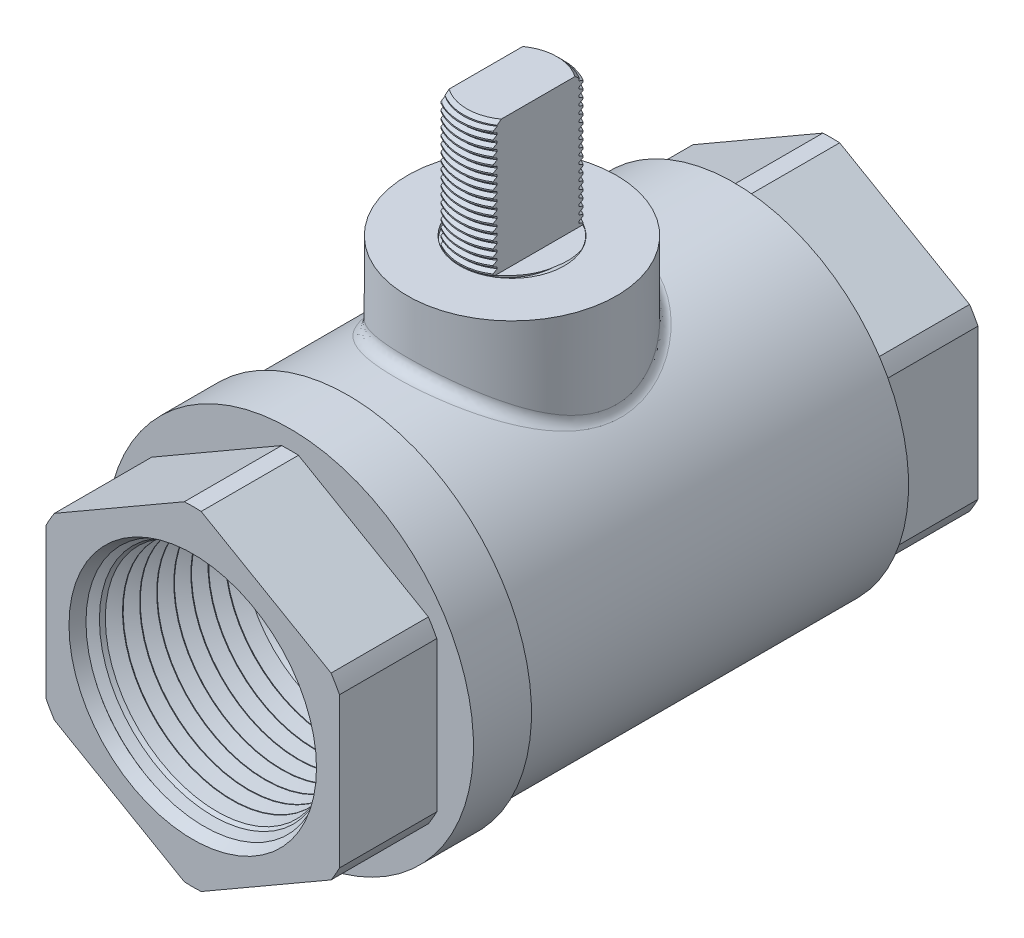
SolidWorks part; units mm, degrees
material "AISI 316 Stainless Steel Sheet (SS)"
ref_plane "Front" through (0, 0, 0) normal (0, 0, 1) x (1, 0, 0)
ref_plane "Top" through (0, 0, 0) normal (0, 1, 0) x (1, 0, 0)
ref_plane "Right" through (0, 0, 0) normal (1, 0, 0) x (0, 0, -1)
sketch "Sketch1" plane through (0, -2.9295, 125.5668) normal (1, 0, 0) x (0, 0, -1)
  line L0 (143.4992, 2.9295) -> (143.4992, 14.4244)
  line L1 (143.4992, 14.4244) -> (144.3569, 16.0232) construction
  line L2 (144.3569, 16.0232) -> (145.3126, 14.4811) construction
  line L3 (145.3126, 14.4811) -> (146.1703, 16.0799) construction
  line L4 (146.1703, 16.0799) -> (147.126, 14.5378) construction
  line L5 (145.3453, 14.542) -> (146.1376, 16.0189)
  line L6 (146.1376, 16.0189) -> (146.2067, 16.0211)
  line L7 (146.2067, 16.0211) -> (147.0896, 14.5965)
  line L8 (147.0896, 14.5965) -> (147.1587, 14.5987)
  line L9 (143.4992, 14.4244) -> (147.126, 14.5378) construction
  line L10 (144.3569, 16.0232) -> (146.1703, 16.0799) construction
  line L11 (143.9281, 15.2238) -> (146.6482, 15.3088) construction
  line L12 (143.4992, 2.9295) -> (125.5668, 2.9295) construction
  line L13 (147.1587, 14.5987) -> (147.951, 16.0756)
  line L14 (143.5319, 14.4854) -> (144.3242, 15.9622)
  line L15 (144.3242, 15.9622) -> (144.3933, 15.9644)
  line L16 (144.3933, 15.9644) -> (145.2762, 14.5399)
  line L17 (145.2762, 14.5399) -> (145.3453, 14.542)
  line L18 (143.9281, 15.2238) -> (143.4992, 15.2104) construction
  line L19 (143.4992, 15.2104) -> (143.4992, 14.4244) construction
  line L20 (143.9281, -9.3648) -> (143.4992, -9.3514) construction
  line L21 (143.5319, 14.4854) -> (143.4992, 14.4244)
  line L22 (147.951, 16.0756) -> (148.0201, 16.0777)
  line L23 (148.0201, 16.0777) -> (148.903, 14.6532)
  line L24 (148.903, 14.6532) -> (148.9721, 14.6554)
  line L25 (148.9721, 14.6554) -> (149.7644, 16.1323)
  line L26 (149.7644, 16.1323) -> (149.8335, 16.1344)
  line L27 (149.8335, 16.1344) -> (150.7164, 14.7099)
  line L28 (150.7164, 14.7099) -> (150.7855, 14.712)
  line L29 (150.7855, 14.712) -> (151.5778, 16.1889)
  line L30 (151.5778, 16.1889) -> (151.6469, 16.1911)
  line L31 (151.6469, 16.1911) -> (152.5298, 14.7666)
  line L32 (152.5298, 14.7666) -> (152.5989, 14.7687)
  line L33 (152.5989, 14.7687) -> (153.3912, 16.2456)
  line L34 (153.3912, 16.2456) -> (153.4603, 16.2478)
  line L35 (153.4603, 16.2478) -> (154.3432, 14.8232)
  line L36 (154.3432, 14.8232) -> (154.4123, 14.8254)
  line L37 (154.4123, 14.8254) -> (155.2046, 16.3023)
  line L38 (155.2046, 16.3023) -> (155.2737, 16.3044)
  line L39 (155.2737, 16.3044) -> (156.1566, 14.8799)
  line L40 (156.1566, 14.8799) -> (156.2257, 14.8821)
  line L41 (156.2257, 14.8821) -> (157.018, 16.3589)
  line L42 (157.018, 16.3589) -> (157.0871, 16.3611)
  line L43 (157.0871, 16.3611) -> (157.97, 14.9366)
  line L44 (157.97, 14.9366) -> (158.0391, 14.9387)
  line L45 (158.0391, 14.9387) -> (158.8314, 16.4156)
  line L46 (158.8314, 16.4156) -> (158.9005, 16.4178)
  line L47 (158.9005, 16.4178) -> (159.7834, 14.9932)
  line L48 (159.7834, 14.9932) -> (159.8525, 14.9954)
  line L49 (159.8525, 14.9954) -> (160.6448, 16.4723)
  line L50 (160.6448, 16.4723) -> (160.7139, 16.4744)
  line L51 (160.7139, 16.4744) -> (161.5968, 15.0499)
  line L52 (161.5968, 15.0499) -> (161.6659, 15.0521)
  line L53 (161.6659, 15.0521) -> (162.4582, 16.529)
  line L54 (162.4582, 16.529) -> (162.5273, 16.5311)
  line L55 (162.5273, 16.5311) -> (163.4102, 15.1066)
  line L56 (163.4102, 15.1066) -> (163.4793, 15.1087)
  line L57 (163.4793, 15.1087) -> (164.2716, 16.5856)
  line L58 (164.2716, 16.5856) -> (164.3407, 16.5878)
  line L59 (164.3407, 16.5878) -> (165.2236, 15.1633)
  line L60 (165.2236, 15.1633) -> (165.2927, 15.1654)
  line L61 (165.2927, 15.1654) -> (166.085, 16.6423)
  line L62 (166.085, 16.6423) -> (166.1541, 16.6445)
  line L63 (166.1541, 16.6445) -> (167.037, 15.2199)
  line L64 (167.037, 15.2199) -> (167.1061, 15.2221)
  line L65 (167.1061, 15.2221) -> (167.8984, 16.699)
  line L66 (167.8984, 16.699) -> (167.9675, 16.7011)
  line L67 (167.9675, 16.7011) -> (168.8504, 15.2766)
  line L68 (168.8504, 15.2766) -> (168.9195, 15.2788)
  line L69 (168.9195, 15.2788) -> (169.7118, 16.7556)
  line L70 (169.7118, 16.7556) -> (169.7809, 16.7578)
  line L71 (169.7809, 16.7578) -> (170.6638, 15.3333)
  line L72 (170.6638, 15.3333) -> (170.7329, 15.3354)
  line L73 (143.4992, 2.9295) -> (170.7329, 2.9295)
  line L74 (170.7329, 2.9295) -> (170.7329, 15.3354)
  line L75 (144.3587, 15.9633) -> (144.3569, 16.0232) construction
  line L76 (146.6482, 15.3088) -> (157.3676, 15.6438) construction
  line L77 (157.3676, 15.6438) -> (157.3676, 2.9295) construction
  line L78 (157.3676, 15.6438) -> (160.4918, 15.7414) construction
  line L79 (160.4918, 15.7414) -> (160.4918, 2.9295) construction
  line L84 (157.3676, 14.9177) -> (160.4918, 15.0154) construction
  line L85 (143.4992, 8.677) -> (125.5668, 8.677) construction
  line L86 (125.5668, 8.677) -> (125.5668, 2.9295) construction
  dimension "D1" = 60
  dimension "E0" = 24.5618
  dimension "Thread Pitch" = 1.8143
  dimension "D4" = 3.58
  dimension "L2 Thread Engagement" = 13.8684
  dimension "l Thread Length" = 16.9926
  dimension "Body Length" = 69.85
revolve "Revolve1" add sketch "Sketch1" angle 360 about L12
sketch "Sketch6" plane through (0, 0, 0) normal (1, 0, 0) x (0, 0, -1)
  line L0 (34.925, 0) -> (34.925, 13.538)
  line L1 (34.925, 13.538) -> (45.1661, 13.8581)
  line L2 (45.1661, 13.8581) -> (45.1661, 0)
  line L3 (45.1661, 0) -> (34.925, 0)
  line L4 (34.925, 12.8119) -> (34.925, 0) construction
  line L5 (17.9324, 0) -> (45.1661, 0) construction
  line L6 (45.1661, 0) -> (45.1661, 12.4059) construction
  line L7 (35.0779, 13.5428) -> (35.1471, 13.5449) construction
revolve "Cut-Revolve3" cut sketch "Sketch6" angle 360 about L3
sketch "Sketch7" plane through (0, 0, 0) normal (1, 0, 0) x (0, 0, -1)
  line L0 (31.8008, 11.9882) -> (34.925, 13.538)
  line L1 (34.925, 13.538) -> (34.925, 12.0859)
  line L2 (34.925, 12.0859) -> (31.8008, 11.9882)
  line L3 (34.925, 12.8119) -> (34.925, 0) construction
  line L4 (18.7573, 13.0327) -> (18.8265, 13.0349) construction
  line L5 (31.8008, 11.9882) -> (34.925, 12.0859) construction
  line L6 (17.9324, 0) -> (31.8008, 0) construction
  line L7 (31.8008, 0) -> (31.8008, 11.9882) construction
  line L8 (17.9324, 0) -> (17.9324, 11.4949) construction
  line L9 (0, 0) -> (17.9324, 0)
  line L10 (0, 0) -> (0, 10.16)
  line L11 (0, 10.16) -> (16.5975, 10.16)
  line L12 (17.9324, 0) -> (17.9324, 11.4949)
  line L13 (17.9324, 11.4949) -> (16.5975, 10.16)
  dimension "D1" = 45
  dimension "Min ID" = 20.32
revolve "Revolve3" add sketch "Sketch7" angle 360 about L6
mirror "Mirror2" about plane through (0, 0, 0) normal (0, 0, 1) of bodies 114
sketch "Sketch8" plane through (0, 0, 34.925) normal (0, 0, 1) x (1, 0, 0)
  line L1 (0, 18.5362) -> (-16.0528, 9.2681)
  line L2 (-16.0528, 9.2681) -> (-16.0528, -9.2681)
  line L3 (-16.0528, -9.2681) -> (0, -18.5362)
  line L4 (0, -18.5362) -> (16.0528, -9.2681)
  line L5 (16.0528, -9.2681) -> (16.0528, 9.2681)
  line L6 (16.0528, 9.2681) -> (0, 18.5362)
  circle A0 centre (0, 0) radius 16.0528 construction
  dimension "Body Hex" = 32.1056
extrude "Extrude1" add sketch "Sketch8" against normal up to surface (69.85 mm away) separate body
sketch "Sketch9" plane through (0, 0, 0) normal (1, 0, 0) x (0, 0, -1)
  line L0 (-24.2824, 9.2681) -> (-24.2824, 20.066)
  line L1 (-24.2824, 20.066) -> (-17.9324, 20.066)
  line L2 (-17.9324, 20.066) -> (-17.9324, 19.5009)
  line L3 (-17.9324, 19.5009) -> (-17.5328, 19.1013)
  line L4 (-17.5328, 19.1013) -> (24.2824, 19.1013)
  line L5 (24.2824, 19.1013) -> (24.2824, 9.2681)
  line L6 (24.2824, 9.2681) -> (-24.2824, 9.2681)
  line L7 (34.925, 9.2681) -> (-34.925, 9.2681) construction
  line L8 (0, 0) -> (0, 9.2681) construction
  line L9 (17.9324, 0) -> (17.9324, 11.4949) construction
  line L10 (0, 0) -> (-24.2824, 0) construction
  line L11 (-24.2824, 0) -> (-24.2824, 9.2681) construction
  line L12 (-17.5328, 19.1013) -> (-17.5328, 18.5362) construction
  line L13 (34.925, 18.5362) -> (-34.925, 18.5362) construction
  line L14 (34.925, 12.8119) -> (34.925, 19.1013) construction
  line L15 (34.925, 19.1013) -> (24.2824, 19.1013) construction
  dimension "D1" = 6.35
  dimension "D2" = 40.132
  dimension "D3" = 135
  dimension "D4" = 6.35
revolve "Revolve4" add sketch "Sketch9" angle 360 about L10
sketch "Sketch10" plane through (0, 0, 0) normal (1, 0, 0) x (0, 0, -1)
  line L0 (0, 1.27) -> (0, 25.4259)
  line L1 (5.7023, 26.2133) -> (5.7277, 26.2133) construction
  line L2 (11.43, 26.2133) -> (11.43, 1.27)
  line L3 (11.43, 1.27) -> (0, 1.27)
  line L4 (0, 0) -> (0, 1.27) construction
  line L5 (-12.7, 21.3873) -> (-12.7, 26.4673) construction
  line L6 (-12.7, 26.4673) -> (12.7, 26.4673) construction
  line L7 (12.7, 26.4673) -> (55.4625, 46.4078) construction
  line L8 (-12.7, 21.3873) -> (-15.875, 21.3873) construction
  line L9 (-15.875, 21.3873) -> (-15.875, 29.6423) construction
  line L10 (-15.875, 29.6423) -> (11.9961, 29.6423) construction
  line L11 (11.9961, 29.6423) -> (55.4625, 49.911) construction
  line L12 (55.4625, 49.911) -> (55.4625, 46.4078) construction
  line L13 (24.2824, 19.1013) -> (-17.5328, 19.1013) construction
  line L14 (55.4625, 51.816) -> (55.4625, 44.5028) construction
  line L15 (55.4625, 44.5028) -> (127, 44.5028) construction
  line L16 (127, 44.5028) -> (127, 51.816) construction
  line L17 (127, 51.816) -> (55.4625, 51.816) construction
  line L18 (-1.9394, 29.6423) -> (-1.9394, 26.4673) construction
  line L19 (33.7293, 39.7766) -> (35.0711, 36.8991) construction
  line L20 (-11.43, 26.2133) -> (-11.43, 1.27) construction
  line L22 (55.4625, 44.5028) -> (55.4625, 10.1859) construction
  line L23 (24.2824, 19.1013) -> (-17.5328, 19.1013) construction
  line L26 (5.7023, 26.2133) -> (5.7023, 40.6913)
  line L27 (5.7023, 40.6913) -> (0, 40.6913)
  line L28 (5.7023, 26.2133) -> (5.7023, 25.4513)
  line L29 (5.7023, 25.4513) -> (0, 25.4513)
  line L30 (0, 25.4259) -> (5.7277, 25.4259)
  line L31 (5.7277, 25.4259) -> (5.7277, 26.2133)
  line L32 (5.7277, 26.2133) -> (11.43, 26.2133)
  line L33 (0, 25.4259) -> (0, 25.4513) construction
  line L34 (0, 25.4513) -> (0, 40.6913)
  line L35 (-5.7023, 26.2133) -> (-5.7023, 40.6913) construction
  line L36 (5.7277, 25.4259) -> (5.7277, 10.1859) construction
  line L37 (5.7277, 10.1859) -> (55.4625, 10.1859) construction
  point P26 (55.4625, 48.1594)
  dimension "Handle Height" = 51.816
  dimension "Handle Length" = 127
  dimension "D3" = 22.86
  dimension "D6" = 3.175
  dimension "D7" = 1.27
  dimension "D8" = 0.254
  dimension "D9" = 1.27
  dimension "D11" = 0.0254
  dimension "D12" = 0.0254
  dimension "D13" = 15.24
  dimension "D14" = 0.762
  dimension "D2" = 1.905
  dimension "D4" = 155
  dimension "D10" = 11.4046
  dimension "D15" = 7.112
  dimension "D16" = 8.255
  dimension "D17" = 1.27
revolve "Revolve5" add sketch "Sketch10" angle 360 about L4
chamfer "Chamfer1" distance 0.762 angle 45 1 edges at (0, 40.6913, -5.7023)
fillet "Fillet5" radius 1.27 1 edges at (3.0869, 18.8502, 11.0053) type face fillet first side face at (3.0869, 18.8502, 11.0053) second side face at (3.0869, 18.8502, 11.0053)
sketch "Sketch20" plane through (0, 0, 0) normal (1, 0, 0) x (0, 0, -1)
  line L0 (5.7023, 40.6913) -> (-5.7023, 40.6913) construction
  line L1 (-5.7023, 40.6913) -> (-5.7023, 39.8975) construction
  line L2 (-5.7023, 39.8975) -> (5.7023, 40.6913) construction
  line L3 (5.7023, 40.6913) -> (5.7092, 40.5923) construction
  line L4 (5.7092, 40.5923) -> (5.7574, 39.8995)
  line L5 (5.7574, 39.8995) -> (5.3116, 40.1171)
  line L6 (5.3116, 40.1171) -> (5.2978, 40.315)
  line L7 (5.2978, 40.315) -> (5.7092, 40.5923)
  line L8 (5.3047, 40.2161) -> (5.7333, 40.2459) construction
  line L9 (5.7023, 40.6913) -> (5.7023, 40.2437) construction
  line L10 (5.7023, 40.2437) -> (-5.7023, 39.45) construction
  line L11 (-5.7023, 39.45) -> (-5.7023, 39.8975) construction
  line L12 (-0.0588, 40.6913) -> (0.0588, 39.0024) construction
  line L13 (-5.7023, 26.2133) -> (-5.7023, 40.6913) construction
  line L14 (5.7023, 26.2133) -> (5.7023, 40.6913) construction
  line L15 (5.7023, 40.6913) -> (0, 40.6913) construction
  point P13 (0, 39.8469)
  dimension "D1" = 0.0992
  dimension "D2" = 0.1984
  dimension "D3" = 0.7937
  dimension "D4" = 60
  dimension "D5" = 0.7937
revolve "Cut-Revolve6" cut sketch "Sketch20" angle 360 about L12
pattern_linear "LPattern1" count 2 spacing 0.7937 along (0, 1, 0) count 19 spacing 0.7937 along (0, -1, 0) of "Cut-Revolve6"
sketch "Sketch26" plane through (0, 25.4259, 0) normal (0, 1, 0) x (-1, 0, 0)
  circle A1 centre (0, 0) radius 5.7277
  circle A2 centre (0, 0) radius 5.7277
  dimension "D1" = 0
extrude "Extrude8" add sketch "Sketch26" along normal blind 0.127
sketch "Sketch16" plane through (0, 0, 0) normal (1, 0, 0) x (0, 0, -1)
  line L0 (-34.925, 9.2681) -> (-34.925, 18.5362) construction
  line L1 (34.925, 18.5362) -> (24.2824, 18.5362)
  line L2 (34.925, 18.5362) -> (34.925, 18.0282)
  line L3 (34.925, 18.0282) -> (24.2824, 18.0282)
  line L4 (24.2824, 18.5362) -> (24.2824, 18.0282)
  line L5 (-34.925, 18.5362) -> (-24.2824, 18.5362)
  line L6 (-34.925, 18.5362) -> (-34.925, 18.0282)
  line L7 (-34.925, 18.0282) -> (-24.2824, 18.0282)
  line L8 (-24.2824, 18.5362) -> (-24.2824, 18.0282)
  line L9 (34.925, 18.5362) -> (34.925, 9.2681) construction
  line L10 (24.2824, -19.1013) -> (24.2824, 19.1013) construction
  line L11 (-24.2824, 20.066) -> (-24.2824, -20.066) construction
  line L12 (-24.2824, 18.5362) -> (-34.925, 18.5362) construction
  line L13 (0, 0) -> (-34.925, 0) construction
  line L14 (-34.925, 0) -> (-34.925, 18.0282) construction
  dimension "D1" = 0.508
revolve "Cut-Revolve5" cut sketch "Sketch16" angle 360 about L13
combine bodies "Combine1" operation type subtract main body 126 bodies to subtract 115
ref_plane "Plane2" through (0, 40.6913, 0) normal (0, 1, 0) x (-1, 0, 0)
sketch "Sketch27" plane through (0, 40.6913, 0) normal (0, 1, 0) x (-1, 0, 0)
  line L0 (-2.8511, -5.7023) -> (2.8511, 5.7023) construction
  line L1 (-2.8511, 5.7023) -> (2.8511, 5.7023)
  line L2 (-2.8511, 5.7023) -> (-2.8511, -5.7023)
  line L3 (-2.8511, -5.7023) -> (2.8511, -5.7023)
  line L4 (2.8511, 5.7023) -> (2.8511, -5.7023)
  dimension "D1" = 5.7023
extrude "Cut-Extrude3" cut sketch "Sketch27" against normal up to surface (14.478 mm away) flip side to cut up to face at (0, 26.2133, -5.7277)
sketch "Sketch11" plane through (0, 0, 0) normal (1, 0, 0) x (0, 0, -1)
  line L1 (11.9961, 29.6423) -> (55.4625, 49.911) construction
  line L2 (12.7, 26.4673) -> (55.4625, 46.4078) construction
  line L3 (-12.7, 26.4673) -> (12.7, 26.4673) construction
  line L4 (-12.7, 21.3873) -> (-12.7, 26.4673) construction
  line L5 (-15.875, 29.6423) -> (11.9961, 29.6423) construction
  line L6 (-15.875, 21.3873) -> (-15.875, 29.6423) construction
  line L7 (125.095, 46.4078) -> (125.095, 49.911)
  line L8 (11.9961, 29.6423) -> (55.4625, 49.911)
  line L9 (12.7, 26.4673) -> (55.4625, 46.4078)
  line L10 (-12.7, 26.4673) -> (12.7, 26.4673)
  line L11 (-12.7, 21.3873) -> (-12.7, 26.4673)
  line L12 (-15.875, 29.6423) -> (11.9961, 29.6423)
  line L13 (-15.875, 21.3873) -> (-15.875, 29.6423)
  line L14 (-12.7, 21.3873) -> (-15.875, 21.3873) construction
  line L15 (-12.7, 21.3873) -> (-15.875, 21.3873)
  line L16 (55.4625, 49.911) -> (125.095, 49.911)
  line L17 (55.4625, 46.4078) -> (125.095, 46.4078)
  line L18 (127, 44.5028) -> (127, 51.816) construction
  dimension "D1" = 1.905
ref_axis "Axis2" through (0, -23.6601, 0) along (0, 1, 0)
sketch "Sketch28" plane through (0, 40.6913, 0) normal (0, 1, 0) x (1, 0, 0)
  circle A0 centre (0, 0) radius 6.35 construction
  dimension "D1" = 12.7
equation "\"D2@Sketch1\"=\"Thread Pitch@Sketch1\"*.033"
equation "\"D2@Sketch9\"=\"Body Hex@Sketch8\"*1.25"
equation "\"D1@Sketch9\" = \"Thread Pitch@Sketch1\"*3.5"
equation "\"D4@Sketch9\"=\"D1@Sketch9\""
equation "\"D2@LPattern1\"=\"D13@Sketch10\"/\"D3@Sketch20\""
